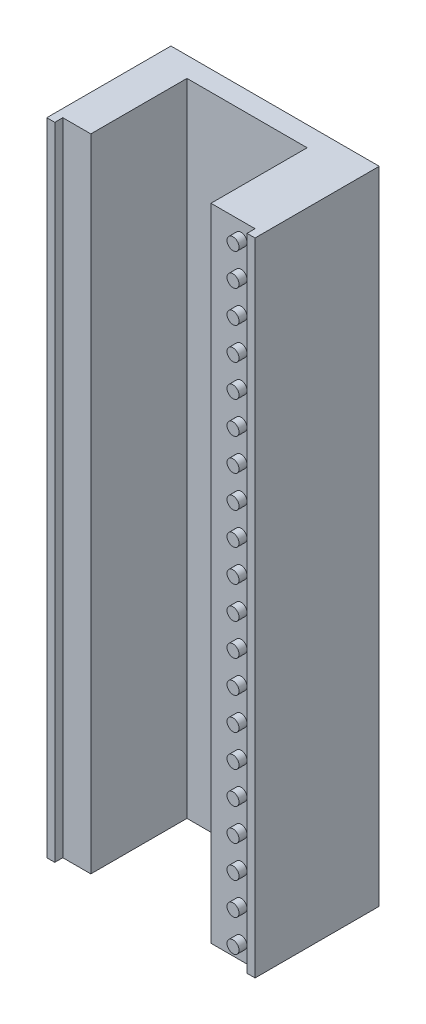
SolidWorks part; units mm, degrees
ref_plane "Top" through (0, 0, 0) normal (0, 0, 1) x (1, 0, 0)
ref_plane "Front" through (0, 0, 0) normal (0, 1, 0) x (1, 0, 0)
ref_plane "Right" through (0, 0, 0) normal (1, 0, 0) x (0, 0, -1)
sketch "Profile Sketch" plane through (0.0456, 0, -0.0242) normal (0, 1, 0) x (-1, 0, 0)
  line L0 (5.5456, -11.9758) -> (5.5456, 0.0242)
  line L1 (5.5456, 0.0242) -> (0.0456, 0.0242)
  line L2 (-0.9544, 1.0242) -> (-0.9544, -14.4758)
  line L3 (-0.9544, -14.4758) -> (25.0456, -14.4758)
  line L4 (5.5456, -11.9758) -> (20.5456, -11.9758)
  line L5 (25.0456, -14.4758) -> (25.0456, 1.0242)
  line L6 (24.0456, 0.0242) -> (20.5456, 0.0242)
  line L7 (20.5456, 0.0242) -> (20.5456, -11.9758)
  line L8 (0.0456, 0.0242) -> (0.0456, 1.0242)
  line L9 (-0.9544, 1.0242) -> (0.0456, 1.0242)
  line L10 (24.0456, 0.0242) -> (24.0456, 1.0242)
  line L11 (24.0456, 1.0242) -> (25.0456, 1.0242)
  line L12 (24.0456, 0.0242) -> (24.0456, 1.0242) construction
  dimension "Sprocket Height" = 1
  dimension "Tape Depth" = 12
  dimension "D8" = 0
  dimension "Reel Width" = 24
  dimension "D4" = 0
  dimension "Wall Thickness" = 1
  dimension "D1" = 14.5
  dimension "D2" = 5.5
  dimension "D3" = 3.5
extrude "Profile Extrude" add sketch "Profile Sketch" along normal blind 80
sketch "Sprocket Sketch" plane through (0, 0, 0) normal (0, 0, 1) x (1, 0, 0)
  line L0 (0, 80) -> (0, 0) construction
  circle A0 centre (-1.75, 2) radius 0.75
  dimension "D2" = 1.5
  dimension "D3" = 2
  dimension "D1" = 1.75
extrude "Sprocket Extrude" add sketch "Sprocket Sketch" along normal blind 1 contours A0
pattern_linear "Sprocket Pattern" count 20 spacing 4 along (0, 1, 0) of "Sprocket Extrude"
ref_plane "Mid Plane" [suppressed] through (0, 40, 0) normal (0, -1, 0) x (-1, 0, 0)
sketch "Magnet Hole Sketch" plane through (0, 0, -12) normal (0, 0, 1) x (1, 0, 0)
  line L0 (-13, 0) -> (-13, 10) construction
  line L1 (-20.5, 0) -> (-5.5, 0) construction
  line L2 (-13, 10) -> (-13, 13.5) construction
  line L3 (-13, 10) -> (-9.6713, 11.0816) construction
  circle A0 centre (-13, 10) radius 2.75 construction
  circle A1 centre (-13, 10) radius 4.75 construction
  arc A2 (-11.151, 12.9718) -> (-13, 13.5) centre (-11.9537, 13.6623) cw
  arc A3 (-11.151, 12.9718) -> (-9.6713, 11.0816) centre (-10.2234, 12.1737) cw
  circle A4 centre (-13, 10) radius 3.5 construction
  arc A5 (-9.6023, 9.1599) -> (-10.9428, 7.1684) centre (-10.0747, 8.031) cw
  arc A6 (-9.6023, 9.1599) -> (-9.6713, 11.0816) centre (-9.1936, 10.1366) cw
  arc A7 (-12.7491, 6.509) -> (-15.0572, 7.1684) centre (-13.9687, 6.6094) cw
  arc A8 (-12.7491, 6.509) -> (-10.9428, 7.1684) centre (-11.6938, 6.4222) cw
  arc A9 (-16.2426, 8.6826) -> (-16.3287, 11.0816) centre (-16.524, 9.8735) cw
  arc A10 (-16.2426, 8.6826) -> (-15.0572, 7.1684) centre (-15.9991, 7.6522) cw
  arc A11 (-15.2549, 12.6768) -> (-13, 13.5) centre (-14.2093, 13.3124) cw
  arc A12 (-15.2549, 12.6768) -> (-16.3287, 11.0816) centre (-16.1597, 12.1268) cw
  point P35 (-13, 10)
  dimension "D2" = 5.5
  dimension "D3" = 0.75
  dimension "D4" = 1.25
  dimension "D1" = 10
  dimension "D5" = 72
  dimension "D6" = 5
extrude "Magnet Cut" [suppressed] cut sketch "Magnet Hole Sketch" against normal through all
chamfer "Magnet Chamfer" [suppressed] distance 0.75 angle 45
mirror "Magnet Mirror" [suppressed] about plane through (0, 40, 0) normal (0, -1, 0)
equation "\"Tape Clearance\"= 0mm'0.15mm works for 0.4 mm nozzles on my printer."
equation "\"D8@Profile Sketch\"=\"Tape Clearance\""
equation "\"D4@Profile Sketch\"=\"Tape Clearance\""
equation "\"D2@Sprocket Sketch\"=1.50mm - 2* \"Sprocket Clearance\""
equation "\"Sprocket Clearance\" = 0mm'0.4mm works for 0.4 mm nozzles on my printer."
equation "\"D1@Sprocket Sketch\"=\"Tape Clearance\"+1.75"
